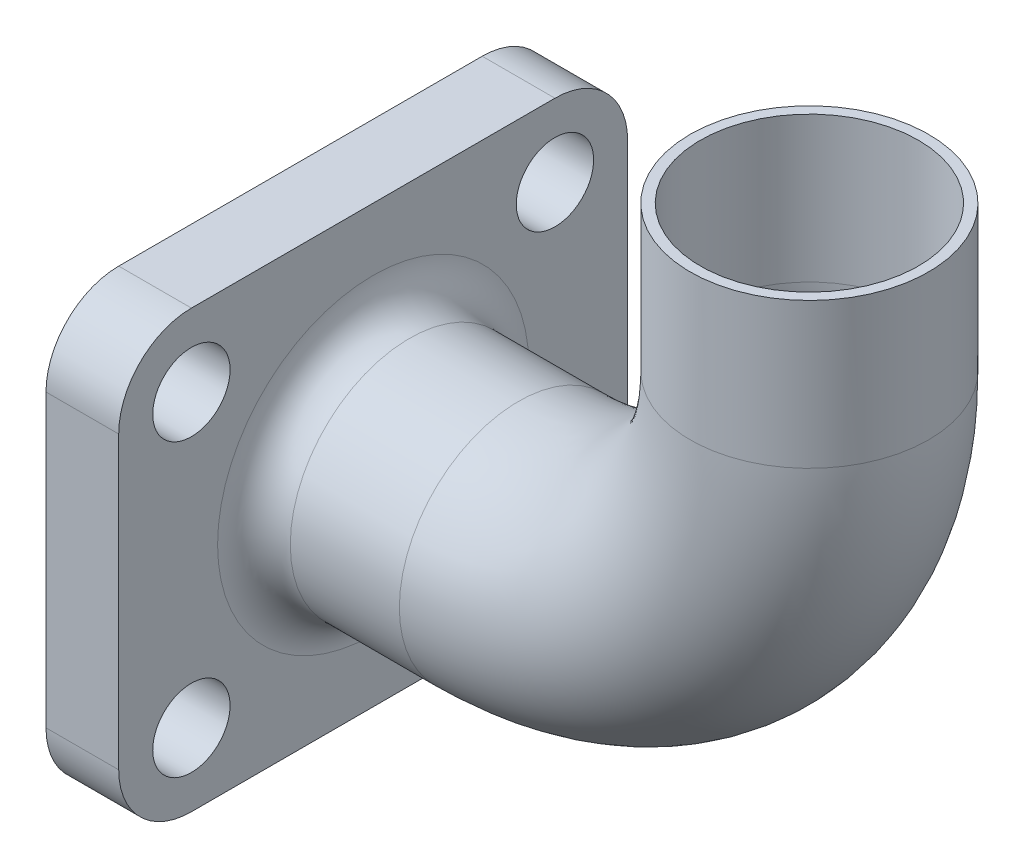
SolidWorks part; units mm, degrees
material "Chrome Stainless Steel"
ref_plane "Front Plane" through (0, 0, 0) normal (0, 0, 1) x (1, 0, 0)
ref_plane "Top Plane" through (0, 0, 0) normal (0, 1, 0) x (1, 0, 0)
ref_plane "Right Plane" through (0, 0, 0) normal (1, 0, 0) x (0, 0, -1)
sketch "Base Sketch" plane through (0, 0, 0) normal (1, 0, 0) x (0, 0, -1)
  line L1 (15.875, -19.05) -> (-15.875, -19.05)
  line L2 (22.225, -12.7) -> (22.225, 12.7)
  line L3 (15.875, 19.05) -> (-15.875, 19.05)
  line L4 (-22.225, -12.7) -> (-22.225, 12.7)
  line L5 (22.225, -19.05) -> (-22.225, 19.05) construction
  line L6 (22.225, 19.05) -> (-22.225, -19.05) construction
  arc A0 (-15.875, -19.05) -> (-22.225, -12.7) centre (-15.875, -12.7) cw
  arc A1 (15.875, -19.05) -> (22.225, -12.7) centre (15.875, -12.7) ccw
  arc A2 (15.875, 19.05) -> (22.225, 12.7) centre (15.875, 12.7) cw
  arc A3 (-15.875, 19.05) -> (-22.225, 12.7) centre (-15.875, 12.7) ccw
  point P0 (0, 0)
  dimension "D3" = 6.35
  dimension "D1" = 44.45
  dimension "D2" = 38.1
extrude "Base" add sketch "Base Sketch" along normal blind 6.35
sketch "Path Sketch" plane through (0, 0, 0) normal (0, 0, 1) x (1, 0, 0)
  line L0 (6.35, 0) -> (19.05, 0)
  line L1 (6.35, 12.7) -> (6.35, -12.7) construction
  line L2 (44.45, 25.4) -> (44.45, 38.1)
  arc A0 (19.05, 0) -> (44.45, 25.4) centre (19.05, 25.4) ccw
  dimension "D3" = 25.4
  dimension "D1" = 38.1
  dimension "D2" = 38.1
sketch "Side Sketch" plane through (0, 0, 0) normal (-1, 0, 0) x (0, 0, 1)
  circle A0 centre (0, 0) radius 12.7
  dimension "D1" = 25.4
extrude "Side Extrude" add sketch "Side Sketch" along normal blind 2.921
sketch "Pipe Sketch" plane through (6.35, 0, 0) normal (1, 0, 0) x (0, 0, -1)
  circle A0 centre (0, 0) radius 9.525
  point P2 (0, 0)
  dimension "D1" = 19.05
sweep "Curved Pipe" add profiles "Pipe Sketch" path "Path Sketch" parameters "D1"=0.889
sketch "Cut Sketch" plane through (-2.921, 0, 0) normal (-1, 0, 0) x (0, 0, 1)
  circle A0 centre (0, 0) radius 9.525
  dimension "D1" = 19.05
extrude "Center Cut" cut sketch "Cut Sketch" against normal up to surface (9.271 mm away) up to face at (6.35, 0, -10.414)
sketch "Corner Sketch" plane through (6.35, 0, 0) normal (1, 0, 0) x (0, 0, -1)
  line L0 (0, 38.1) -> (0, -19.05) construction
  line L1 (10.414, 38.1) -> (-10.414, 38.1) construction
  line L2 (-15.875, -19.05) -> (15.875, -19.05) construction
  line L3 (-22.225, 0) -> (22.225, 0) construction
  line L4 (-22.225, 12.7) -> (-22.225, -12.7) construction
  line L5 (22.225, -12.7) -> (22.225, 12.7) construction
  circle A0 centre (-15.875, 12.7) radius 3.3782
  circle A1 centre (15.875, 12.7) radius 3.3782
  circle A2 centre (15.875, -12.7) radius 3.3782
  circle A3 centre (-15.875, -12.7) radius 3.3782
  dimension "D1" = 6.7564
extrude "Corner Holes" cut sketch "Corner Sketch" against normal through all
fillet "Base Fillet" radius 3.175 1 edges at (6.35, 0, -10.414)
